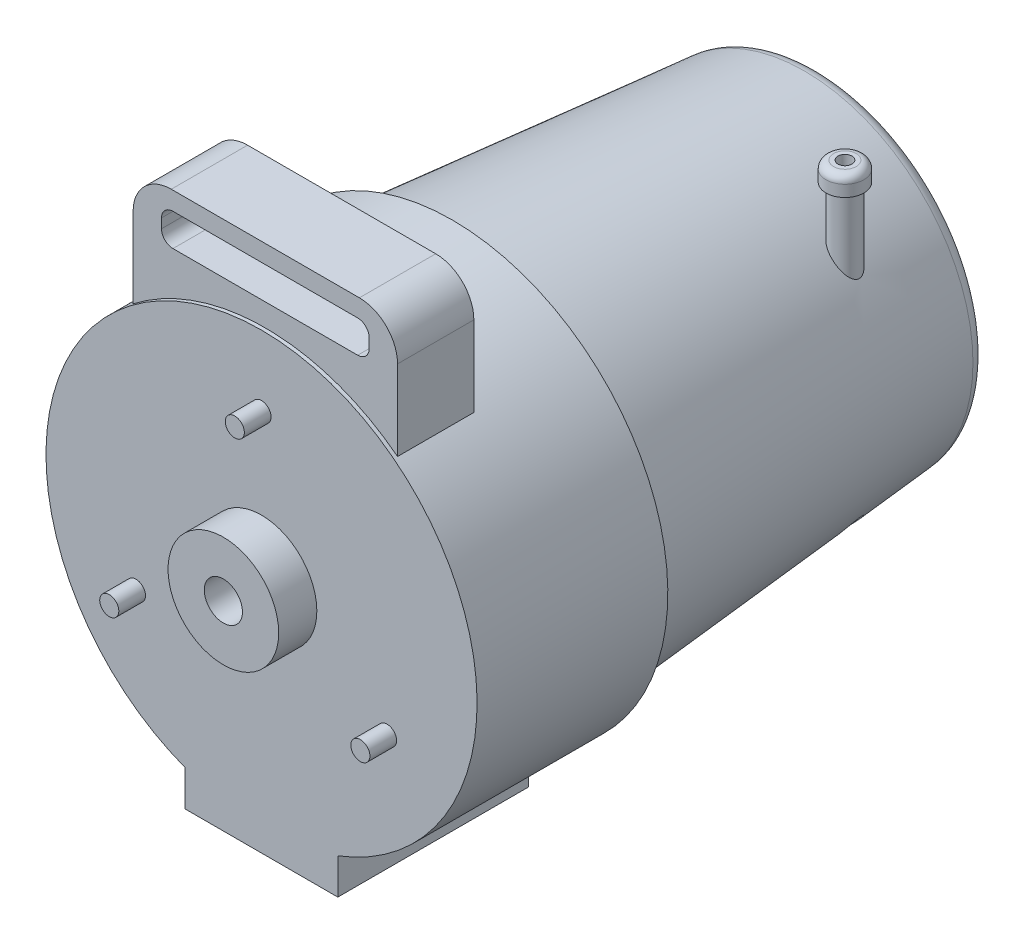
SolidWorks part; units mm, degrees
ref_plane "Front Plane" through (0, 0, 0) normal (0, 0, 1) x (1, 0, 0)
ref_plane "Top Plane" through (0, 0, 0) normal (0, 1, 0) x (1, 0, 0)
ref_plane "Right Plane" through (0, 0, 0) normal (1, 0, 0) x (0, 0, -1)
sketch "Sketch1" plane through (0, 0, 0) normal (0, 0, 1) x (1, 0, 0)
  line L0 (-20, -52.8417) -> (-20, -62.22)
  line L1 (-20, -62.22) -> (20, -62.22)
  line L2 (20, -62.22) -> (20, -52.8417)
  arc A0 (20, -52.8417) -> (-20, -52.8417) centre (0, 0) ccw
  circle A1 centre (0, 0) radius 5
  point P1 (0, -62.22)
  dimension "D1" = 56.5
  dimension "D4" = 10
  dimension "D2" = 40
  dimension "D3" = 62.22
extrude "Boss-Extrude1" add sketch "Sketch1" against normal blind 50
sketch "Sketch2" plane through (0, 0, 0) normal (0, 0, 1) x (1, 0, 0)
  circle A0 centre (0, 0) radius 14.5
  circle A1 centre (0, 0) radius 5 construction
  circle A2 centre (0, 0) radius 5
  dimension "D1" = 29
extrude "Boss-Extrude2" add sketch "Sketch2" along normal blind 10
sketch "Sketch3" plane through (0, 0, 0) normal (1, 0, 0) x (0, 0, -1)
  line L0 (146, 40.15) -> (146, -40.15)
  line L1 (142.3486, 44.1348) -> (50, 52.2142)
  line L2 (50, -52.8417) -> (50, 56.5) construction
  line L3 (0, 0) -> (146, 0) construction
  line L4 (0, 14.5) -> (0, -14.5) construction
  line L5 (142.3486, -44.1348) -> (50, -52.2142)
  line L6 (50, 52.2142) -> (50, -52.2142)
  line L7 (50, 0) -> (146, 0)
  arc A0 (146, 40.15) -> (142.3486, 44.1348) centre (142, 40.15) ccw
  arc A1 (146, -40.15) -> (142.3486, -44.1348) centre (142, -40.15) cw
  point P2 (146, 0)
  point P16 (146, 43.8153)
  point P19 (146, -43.8153)
  dimension "D4" = 4
  dimension "D1" = 40.15
  dimension "D2" = 156
  dimension "D3" = 5
revolve "Revolve1" add sketch "Sketch3" angle 360 about L3 region at (0, -24.0571, -96.5711)
sketch "Sketch4" plane through (0, 0, 0) normal (0, 0, 1) x (1, 0, 0)
  line L0 (-24.655, 75.65) -> (24.655, 75.65)
  line L1 (-20, -62.22) -> (20, -62.22) construction
  line L2 (34.655, 65.65) -> (34.655, 44.6238)
  line L3 (-34.655, 65.65) -> (-34.655, 44.6238)
  line L5 (-24.21, 70.86) -> (24.21, 70.86)
  line L6 (-27.21, 67.86) -> (-27.21, 65.4)
  line L7 (-24.21, 62.4) -> (24.21, 62.4)
  line L8 (27.21, 67.86) -> (27.21, 65.4)
  arc A0 (20, -52.8417) -> (-20, -52.8417) centre (0, 0) ccw construction
  arc A1 (-24.655, 75.65) -> (-34.655, 65.65) centre (-24.655, 65.65) ccw
  arc A2 (24.655, 75.65) -> (34.655, 65.65) centre (24.655, 65.65) cw
  arc A3 (34.655, 44.6238) -> (-20, -52.8417) centre (0, 0) ccw
  arc A4 (-27.21, 65.4) -> (-24.21, 62.4) centre (-24.21, 65.4) ccw
  arc A5 (-24.21, 70.86) -> (-27.21, 67.86) centre (-24.21, 67.86) ccw
  arc A6 (24.21, 62.4) -> (27.21, 65.4) centre (24.21, 65.4) ccw
  arc A7 (24.21, 70.86) -> (27.21, 67.86) centre (24.21, 67.86) cw
  point P2 (0, 75.65)
  point P13 (-34.655, 75.65)
  point P16 (34.655, 75.65)
  point P29 (0, 62.4)
  arc M1 (20, -52.8417) -> (-20, -52.8417) centre (0, 0) ccw
  dimension "D3" = 10
  dimension "D4" = 3
  dimension "D1" = 69.31
  dimension "D2" = 137.87
  dimension "D5" = 8.46
  dimension "D6" = 54.42
  dimension "D7" = 4.79
extrude "Boss-Extrude3" add sketch "Sketch4" against normal blind 20 from offset 1 contours A2 L0 A1 L3 L2 L5 A7 L8 A6 L7 A4 L6 A5 M1 region at (0, 74.8906, 0) offset against normal yes
sketch "Sketch5" plane through (0, 0, 0) normal (0, 0, 1) x (1, 0, 0)
  circle A0 centre (0, 38) radius 2.5
  circle A1 centre (32.909, -19) radius 2.5
  circle A2 centre (-32.909, -19) radius 2.5
  point P9 (0, 0)
  dimension "D2" = 5
  dimension "D1" = 38
  dimension "D3" = 3
extrude "Boss-Extrude4" add sketch "Sketch5" along normal blind 7
sketch "Sketch6" plane through (0, 0, 0) normal (1, 0, 0) x (0, 0, -1)
  line L0 (21, 51.7399) -> (21, 42.51)
  line L1 (143, -3.5) -> (146, -3.5)
  line L2 (50, 52.2142) -> (142.3486, 44.1348)
  line L3 (142.3486, -44.1348) -> (50, -52.2142)
  line L4 (142.3486, -44.1348) -> (50, -52.2142)
  line L5 (21, 54.7514) -> (142.3486, 44.1348) construction
  line L6 (146, 40.15) -> (146, 0) construction
  line L7 (146, -40.15) -> (146, 40.15) construction
  line L8 (146, 0) -> (-10, 0) construction
  line L9 (-10, 5) -> (-10, -5) construction
  line L10 (21, 51.7399) -> (142.0872, 41.1462)
  line L11 (143, 40.15) -> (143, 0)
  line L12 (143, -41.0663) -> (143, -3.5)
  line L13 (50, -49.2028) -> (143, -41.0663)
  line L14 (146, -3.5) -> (146, 0)
  line L15 (0, -52.8417) -> (0, -62.22) construction
  line L16 (21, 42.51) -> (3, 42.51)
  line L17 (3, 42.51) -> (3, -47.3528)
  line L18 (0, 56.5) -> (0, -52.8417) construction
  line L19 (1, 75.65) -> (1, 65.65) construction
  line L20 (3, -47.3528) -> (50, -47.3528)
  line L21 (50, -52.2142) -> (50, 52.2142) construction
  line L22 (50, -47.3528) -> (50, -49.2028)
  line L23 (49.7385, 49.2257) -> (142.0872, 41.1462) construction
  line L24 (50, 52.2142) -> (50, 60.1642)
  line L25 (50, -52.8417) -> (50, 56.5) construction
  line L26 (50, 60.1642) -> (21, 60.1642)
  line L27 (21, 44.6238) -> (21, 56.5) construction
  line L28 (21, 60.1642) -> (21, 54.7514)
  line L29 (50, 52.2142) -> (142.3486, 44.1348) construction
  line L30 (21, 54.7514) -> (50, 52.2142)
  line L31 (146, 0) -> (3, 0)
  arc A0 (146, 40.15) -> (142.3486, 44.1348) centre (142, 40.15) ccw
  arc A1 (142.3486, -44.1348) -> (146, -40.15) centre (142, -40.15) ccw
  arc A2 (142.3486, -44.1348) -> (146, -40.15) centre (142, -40.15) ccw
  arc A3 (146, 40.15) -> (142.3486, 44.1348) centre (142, 40.15) ccw construction
  arc A4 (143, 40.15) -> (142.0872, 41.1462) centre (142, 40.15) ccw
  point P18 (0, -57.5309)
  point P26 (1, 70.65)
  dimension "D2" = 50
  dimension "D3" = 1.85
  dimension "D4" = 3
  dimension "D5" = 20
  dimension "D6" = 42.51
  dimension "D7" = 7.95
  dimension "D8" = 3.5
  dimension "D1" = 3
revolve "Cut-Revolve1" cut sketch "Sketch6" angle 360 about L31 region at (0, -22.9569, -71.4516)
fillet "Fillet1" radius 1 1 edges at (0, 3.5, -146)
sketch "Sketch32" plane through (0, 0, -50) normal (0, 0, -1) x (-1, 0, 0)
  circle A0 centre (0, 0) radius 47.3528 construction
  circle A1 centre (0, 0) radius 49.2028
  circle A2 centre (0, 0) radius 49.2028
  circle A3 centre (0, 0) radius 47.3528
  dimension "D1" = 0
extrude "Cut-Extrude16" cut sketch "Sketch32" against normal up to surface (47 mm away) up to face at (0, 47.3528, -3)
ref_plane "Plane1" through (0, -47.35, 0) normal (0, -1, 0) x (-1, 0, 0)
sketch "Sketch33" plane through (0, -47.35, 0) normal (0, -1, 0) x (-1, 0, 0)
  line L0 (-20, 3) -> (20, 3)
  line L1 (49.2028, 3) -> (-49.2028, 3) construction
  line L2 (-20, 3) -> (-20, 14.82)
  line L3 (-20, 14.82) -> (-13.355, 40)
  line L4 (-14.5, -10) -> (14.5, -10) construction
  line L5 (-13.355, 40) -> (13.355, 40)
  line L6 (0, 40) -> (0, 3) construction
  line L8 (13.355, 40) -> (20, 14.82)
  line L9 (20, 14.82) -> (20, 3)
  point P4 (0, 3)
  dimension "D1" = 40
  dimension "D2" = 25.18
  dimension "D3" = 50
  dimension "D4" = 26.71
extrude "Boss-Extrude10" add sketch "Sketch33" against normal blind 1.85
sketch "Sketch35" plane through (0, -45.5, 0) normal (0, 1, 0) x (1, 0, 0)
  line L0 (-13.355, 40) -> (13.355, 40) construction
  circle A0 centre (0, 35.17) radius 2.5
  dimension "D1" = 4.83
  dimension "D2" = 5
extrude "Boss-Extrude11" add sketch "Sketch35" along normal blind 4.98
sketch "Sketch36" plane through (0, -40.52, 0) normal (0, 1, 0) x (1, 0, 0)
  circle A0 centre (0, 35.17) radius 1.25
  dimension "D1" = 2.5
extrude "Boss-Extrude12" add sketch "Sketch36" along normal blind 0.94
sketch "Sketch8" plane through (0, 0, 0) normal (1, 0, 0) x (0, 0, -1)
  line L0 (50, -62.22) -> (0, -62.22) construction
  line L1 (40.205, -62.22) -> (9.795, -62.22)
  line L2 (40.205, -62.22) -> (40.205, -52.22)
  line L3 (9.795, -52.22) -> (40.205, -52.22)
  line L4 (9.795, -62.22) -> (9.795, -52.22)
  point P2 (25, -52.22)
  point P9 (25, -62.22)
  dimension "D1" = 30.41
  dimension "D2" = 10
extrude "Cut-Extrude1" cut sketch "Sketch8" against normal mid plane 12.56
sketch "Sketch9" plane through (0, 0, -146) normal (0, 0, -1) x (-1, 0, 0)
  line L0 (-1.97, 40.1016) -> (-1.97, 31.63)
  line L1 (1.97, 40.1016) -> (1.97, 31.63)
  line L2 (8.4762, 39.2451) -> (6.2836, 31.0621)
  line L3 (12.2819, 38.2253) -> (10.0893, 30.0424)
  line L4 (18.3448, 35.714) -> (14.1089, 28.3774)
  line L5 (21.7569, 33.744) -> (17.5211, 26.4074)
  line L6 (26.9631, 29.7491) -> (20.9728, 23.7588)
  line L7 (29.7491, 26.9631) -> (23.7588, 20.9728)
  line L8 (33.744, 21.7569) -> (26.4074, 17.5211)
  line L9 (35.714, 18.3448) -> (28.3774, 14.1089)
  line L10 (38.2253, 12.2819) -> (30.0424, 10.0893)
  line L11 (39.2451, 8.4762) -> (31.0621, 6.2836)
  line L12 (40.1016, 1.97) -> (31.63, 1.97)
  line L13 (40.1016, -1.97) -> (31.63, -1.97)
  line L14 (39.2451, -8.4762) -> (31.0621, -6.2836)
  line L15 (38.2253, -12.2819) -> (30.0424, -10.0893)
  line L16 (35.714, -18.3448) -> (28.3774, -14.1089)
  line L17 (33.744, -21.7569) -> (26.4074, -17.5211)
  line L18 (29.7491, -26.9631) -> (23.7588, -20.9728)
  line L19 (26.9631, -29.7491) -> (20.9728, -23.7588)
  line L20 (21.7569, -33.744) -> (17.5211, -26.4074)
  line L21 (18.3448, -35.714) -> (14.1089, -28.3774)
  line L22 (12.2819, -38.2253) -> (10.0893, -30.0424)
  line L23 (8.4762, -39.2451) -> (6.2836, -31.0621)
  line L24 (1.97, -40.1016) -> (1.97, -31.63)
  line L25 (-1.97, -40.1016) -> (-1.97, -31.63)
  line L26 (-8.4762, -39.2451) -> (-6.2836, -31.0621)
  line L27 (-12.2819, -38.2253) -> (-10.0893, -30.0424)
  line L28 (-18.3448, -35.714) -> (-14.1089, -28.3774)
  line L29 (-21.7569, -33.744) -> (-17.5211, -26.4074)
  line L30 (-26.9631, -29.7491) -> (-20.9728, -23.7588)
  line L31 (-29.7491, -26.9631) -> (-23.7588, -20.9728)
  line L32 (-33.744, -21.7569) -> (-26.4074, -17.5211)
  line L33 (-35.714, -18.3448) -> (-28.3774, -14.1089)
  line L34 (-38.2253, -12.2819) -> (-30.0424, -10.0893)
  line L35 (-39.2451, -8.4762) -> (-31.0621, -6.2836)
  line L36 (-40.1016, -1.97) -> (-31.63, -1.97)
  line L37 (-40.1016, 1.97) -> (-31.63, 1.97)
  line L38 (-39.2451, 8.4762) -> (-31.0621, 6.2836)
  line L39 (-38.2253, 12.2819) -> (-30.0424, 10.0893)
  line L40 (-35.714, 18.3448) -> (-28.3774, 14.1089)
  line L41 (-33.744, 21.7569) -> (-26.4074, 17.5211)
  line L42 (-29.7491, 26.9631) -> (-23.7588, 20.9728)
  line L43 (-26.9631, 29.7491) -> (-20.9728, 23.7588)
  line L44 (-21.7569, 33.744) -> (-17.5211, 26.4074)
  line L45 (-18.3448, 35.714) -> (-14.1089, 28.3774)
  line L46 (-12.2819, 38.2253) -> (-10.0893, 30.0424)
  line L47 (-8.4762, 39.2451) -> (-6.2836, 31.0621)
  circle A0 centre (0, 0) radius 40.15 construction
  arc A1 (1.97, 40.1016) -> (-1.97, 40.1016) centre (0, 0) ccw
  arc A2 (1.97, 31.63) -> (-1.97, 31.63) centre (0, 31.63) cw
  arc A3 (12.2819, 38.2253) -> (8.4762, 39.2451) centre (0, 0) ccw
  arc A4 (10.0893, 30.0424) -> (6.2836, 31.0621) centre (8.1864, 30.5522) cw
  arc A5 (21.7569, 33.744) -> (18.3448, 35.714) centre (0, 0) ccw
  arc A6 (17.5211, 26.4074) -> (14.1089, 28.3774) centre (15.815, 27.3924) cw
  arc A7 (29.7491, 26.9631) -> (26.9631, 29.7491) centre (0, 0) ccw
  arc A8 (23.7588, 20.9728) -> (20.9728, 23.7588) centre (22.3658, 22.3658) cw
  arc A9 (35.714, 18.3448) -> (33.744, 21.7569) centre (0, 0) ccw
  arc A10 (28.3774, 14.1089) -> (26.4074, 17.5211) centre (27.3924, 15.815) cw
  arc A11 (39.2451, 8.4762) -> (38.2253, 12.2819) centre (0, 0) ccw
  arc A12 (31.0621, 6.2836) -> (30.0424, 10.0893) centre (30.5522, 8.1864) cw
  arc A13 (40.1016, -1.97) -> (40.1016, 1.97) centre (0, 0) ccw
  arc A14 (31.63, -1.97) -> (31.63, 1.97) centre (31.63, 0) cw
  arc A15 (38.2253, -12.2819) -> (39.2451, -8.4762) centre (0, 0) ccw
  arc A16 (30.0424, -10.0893) -> (31.0621, -6.2836) centre (30.5522, -8.1864) cw
  arc A17 (33.744, -21.7569) -> (35.714, -18.3448) centre (0, 0) ccw
  arc A18 (26.4074, -17.5211) -> (28.3774, -14.1089) centre (27.3924, -15.815) cw
  arc A19 (26.9631, -29.7491) -> (29.7491, -26.9631) centre (0, 0) ccw
  arc A20 (20.9728, -23.7588) -> (23.7588, -20.9728) centre (22.3658, -22.3658) cw
  arc A21 (18.3448, -35.714) -> (21.7569, -33.744) centre (0, 0) ccw
  arc A22 (14.1089, -28.3774) -> (17.5211, -26.4074) centre (15.815, -27.3924) cw
  arc A23 (8.4762, -39.2451) -> (12.2819, -38.2253) centre (0, 0) ccw
  arc A24 (6.2836, -31.0621) -> (10.0893, -30.0424) centre (8.1864, -30.5522) cw
  arc A25 (-1.97, -40.1016) -> (1.97, -40.1016) centre (0, 0) ccw
  arc A26 (-1.97, -31.63) -> (1.97, -31.63) centre (0, -31.63) cw
  arc A27 (-12.2819, -38.2253) -> (-8.4762, -39.2451) centre (0, 0) ccw
  arc A28 (-10.0893, -30.0424) -> (-6.2836, -31.0621) centre (-8.1864, -30.5522) cw
  arc A29 (-21.7569, -33.744) -> (-18.3448, -35.714) centre (0, 0) ccw
  arc A30 (-17.5211, -26.4074) -> (-14.1089, -28.3774) centre (-15.815, -27.3924) cw
  arc A31 (-29.7491, -26.9631) -> (-26.9631, -29.7491) centre (0, 0) ccw
  arc A32 (-23.7588, -20.9728) -> (-20.9728, -23.7588) centre (-22.3658, -22.3658) cw
  arc A33 (-35.714, -18.3448) -> (-33.744, -21.7569) centre (0, 0) ccw
  arc A34 (-28.3774, -14.1089) -> (-26.4074, -17.5211) centre (-27.3924, -15.815) cw
  arc A35 (-39.2451, -8.4762) -> (-38.2253, -12.2819) centre (0, 0) ccw
  arc A36 (-31.0621, -6.2836) -> (-30.0424, -10.0893) centre (-30.5522, -8.1864) cw
  arc A37 (-40.1016, 1.97) -> (-40.1016, -1.97) centre (0, 0) ccw
  arc A38 (-31.63, 1.97) -> (-31.63, -1.97) centre (-31.63, 0) cw
  arc A39 (-38.2253, 12.2819) -> (-39.2451, 8.4762) centre (0, 0) ccw
  arc A40 (-30.0424, 10.0893) -> (-31.0621, 6.2836) centre (-30.5522, 8.1864) cw
  arc A41 (-33.744, 21.7569) -> (-35.714, 18.3448) centre (0, 0) ccw
  arc A42 (-26.4074, 17.5211) -> (-28.3774, 14.1089) centre (-27.3924, 15.815) cw
  arc A43 (-26.9631, 29.7491) -> (-29.7491, 26.9631) centre (0, 0) ccw
  arc A44 (-20.9728, 23.7588) -> (-23.7588, 20.9728) centre (-22.3658, 22.3658) cw
  arc A45 (-18.3448, 35.714) -> (-21.7569, 33.744) centre (0, 0) ccw
  arc A46 (-14.1089, 28.3774) -> (-17.5211, 26.4074) centre (-15.815, 27.3924) cw
  arc A47 (-8.4762, 39.2451) -> (-12.2819, 38.2253) centre (0, 0) ccw
  arc A48 (-6.2836, 31.0621) -> (-10.0893, 30.0424) centre (-8.1864, 30.5522) cw
  point P6 (0, 40.15)
  point P126 (0, 0)
  dimension "D2" = 31.63
  dimension "D1" = 3.94
  dimension "D3" = 24
extrude "Cut-Extrude2" cut sketch "Sketch9" against normal up to next
sketch "Sketch10" plane through (0, 0, 0) normal (1, 0, 0) x (0, 0, -1)
  line L1 (136, 15.645) -> (102.31, 15.645)
  line L2 (136, 15.645) -> (136, -15.645)
  line L3 (136, -15.645) -> (102.31, -15.645)
  line L4 (102.31, 15.645) -> (102.31, -15.645)
  point P4 (136, 0)
  dimension "D1" = 31.29
  dimension "D2" = 33.69
  dimension "D3" = 10
extrude "Boss-Extrude5" add sketch "Sketch10" along normal up to next and the other way up to next
sketch "Sketch25" plane through (0, 15.645, 0) normal (0, 1, 0) x (1, 0, 0)
  spline S0 degree 3 poles (434.6388, -1851.3988) (-139.9186, -577.6251) (257.2224, 800.373) (-457.759, 2061.0969) knots -58.665848 -58.665848 -58.665848 -58.665848 59.107074 59.107074 59.107074 59.107074 only from (41.794, 102.31) to (38.631, 136) construction
  spline S1 degree 3 poles (41.794, 102.31) (40.7166, 113.8432) (39.6341, 125.3759) (38.5453, 136.908) knots 0 0 0 0 1.026952 1.026952 1.026952 1.026952
sketch "Sketch24" plane through (0, 0, -102.31) normal (0, 0, 1) x (1, 0, 0)
  line L2 (-41.794, -15.645) -> (41.794, -15.645)
  line L3 (41.794, 15.645) -> (-41.794, 15.645)
  line L5 (41.794, 15.645) -> (29.0884, 15.645)
  arc A0 (44.5688, 2.2631) -> (29.0884, 15.645) centre (29.0884, 0) ccw
  arc A2 (44.5688, 2.2631) -> (41.794, 15.645) centre (0, 0) ccw
  arc A4 (-41.794, 15.645) -> (-41.794, -15.645) centre (0, 0) ccw
  arc A5 (41.794, -15.645) -> (41.794, 15.645) centre (0, 0) ccw
  dimension "D1" = 31.29
  dimension "D3" = 29.0884
  dimension "D2" = 0
sweep "Cut-Sweep4" cut profiles "Sketch24" path "Sketch25"
mirror "Mirror1" about plane through (0, 0, 0) normal (0, 1, 0) of "Cut-Sweep4"
mirror "Mirror2" about plane through (0, 0, 0) normal (1, 0, 0) of "Mirror1", "Cut-Sweep4"
sketch "Sketch11" plane through (0, 0, -136) normal (0, 0, -1) x (-1, 0, 0)
  circle A0 centre (0, 0) radius 5
  dimension "D1" = 10
extrude "Cut-Extrude3" cut sketch "Sketch11" against normal up to next
sketch "Sketch28" plane through (0, 0, -102.31) normal (0, 0, 1) x (1, 0, 0)
  circle A0 centre (0, 0) radius 18.21
  dimension "D1" = 18.21
extrude "Cut-Extrude14" cut sketch "Sketch28" against normal blind 1.27
sketch "Sketch29" plane through (0, 62.4, 0) normal (0, 1, 0) x (1, 0, 0)
  circle A0 centre (33.77, 119.155) radius 3.54
  dimension "D1" = 33.77
  dimension "D2" = 7.08
  dimension "D3" = 26.845
extrude "Boss-Extrude8" add sketch "Sketch29" against normal up to next from offset 15 offset against normal yes
sketch "Sketch30" plane through (0, 47.4, 0) normal (0, 1, 0) x (1, 0, 0)
  circle A0 centre (33.77, 119.155) radius 4.96
  dimension "D1" = 9.92
extrude "Boss-Extrude9" add sketch "Sketch30" along normal blind 5
fillet "Fillet3" radius 2 1 edges at (33.77, 52.4, -114.195)
sketch "Sketch31" plane through (0, 52.4, 0) normal (0, 1, 0) x (1, 0, 0)
  circle A0 centre (33.77, 119.155) radius 1.835
  dimension "D1" = 3.67
extrude "Cut-Extrude15" cut sketch "Sketch31" against normal blind 25.01
sketch "Sketch37" plane through (0, 0, 0) normal (0, 1, 0) x (1, 0, 0)
  circle A0 centre (33.77, 119.155) radius 3.54 construction
  circle A1 centre (33.77, 119.155) radius 3.54
extrude "Cut-Extrude17" cut sketch "Sketch37" along normal up to next from offset 50 offset against normal yes
sketch "Sketch38" plane through (-20, 0, 0) normal (-1, 0, 0) x (0, 0, 1)
  line L0 (-50, -62.22) -> (0, -62.22) construction
  line L1 (0, -52.8417) -> (0, -62.22) construction
  circle A0 centre (-23.36, -55.98) radius 1.5
  dimension "D1" = 6.24
  dimension "D2" = 3
  dimension "D3" = 23.36
extrude "Cut-Extrude18" cut sketch "Sketch38" against normal through all
